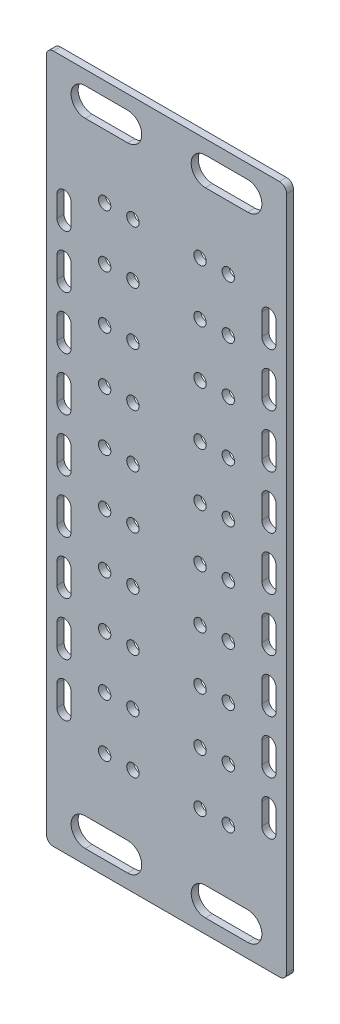
SolidWorks part; units mm, degrees
ref_plane "Plano frontal" through (0, 0, 0) normal (0, 0, 1) x (1, 0, 0)
ref_plane "Plano superior" through (0, 0, 0) normal (0, 1, 0) x (1, 0, 0)
ref_plane "Plano direito" through (0, 0, 0) normal (1, 0, 0) x (0, 0, -1)
sketch "Esboço1" plane through (0, 0, 0) normal (0, 0, 1) x (1, 0, 0)
  line L1 (0, 0) -> (68, 0)
  line L2 (0, 0) -> (0, 195)
  line L3 (0, 195) -> (68, 195)
  line L4 (68, 0) -> (68, 195)
  point P5 (67.3107, 195)
  dimension "D1" = 195
  dimension "D2" = 68
base flange "Flange-base1" sketch "Esboço1" thickness 2 reverse thickness direction no parameters "D1"=0.7366
fillet "Filete1" radius 2 4 edges at (0, 0, -1) (68, 0, -1) (0, 195, -1) (68, 195, -1)
sketch "Esboço2" plane through (0, 0, 0) normal (0, 0, 1) x (1, 0, 0)
  line L0 (11, 187) -> (23, 187) construction
  line L1 (11, 191) -> (23, 191)
  line L2 (11, 183) -> (23, 183)
  line L3 (34, 0) -> (34, 195) construction
  line L4 (2, 0) -> (66, 0) construction
  line L5 (0, 97.5) -> (68, 97.5) construction
  line L6 (0, 193) -> (0, 2) construction
  line L7 (68, 2) -> (68, 193) construction
  line L8 (66, 195) -> (2, 195) construction
  line L9 (5, 160.5) -> (5, 154.5) construction
  line L10 (57, 187) -> (45, 187) construction
  line L11 (57, 191) -> (45, 191)
  line L12 (57, 183) -> (45, 183)
  line L13 (11, 8) -> (23, 8) construction
  line L14 (11, 4) -> (23, 4)
  line L15 (11, 12) -> (23, 12)
  line L16 (57, 8) -> (45, 8) construction
  line L17 (57, 4) -> (45, 4)
  line L18 (57, 12) -> (45, 12)
  line L20 (16.5, 165) -> (24.5, 165) construction
  line L21 (7, 160.5) -> (7, 154.5)
  line L22 (3, 160.5) -> (3, 154.5)
  line L23 (16.5, 165) -> (16.5, 150) construction
  line L24 (63, 160.5) -> (63, 154.5) construction
  line L25 (65, 160.5) -> (65, 154.5)
  line L26 (61, 160.5) -> (61, 154.5)
  line L27 (63, 145.5) -> (63, 139.5) construction
  line L28 (65, 145.5) -> (65, 139.5)
  line L29 (61, 145.5) -> (61, 139.5)
  line L30 (63, 130.5) -> (63, 124.5) construction
  line L31 (65, 130.5) -> (65, 124.5)
  line L32 (61, 130.5) -> (61, 124.5)
  line L33 (63, 115.5) -> (63, 109.5) construction
  line L34 (65, 115.5) -> (65, 109.5)
  line L35 (61, 115.5) -> (61, 109.5)
  line L36 (63, 100.5) -> (63, 94.5) construction
  line L37 (65, 100.5) -> (65, 94.5)
  line L38 (61, 100.5) -> (61, 94.5)
  line L39 (63, 85.5) -> (63, 79.5) construction
  line L40 (65, 85.5) -> (65, 79.5)
  line L41 (61, 85.5) -> (61, 79.5)
  line L42 (63, 70.5) -> (63, 64.5) construction
  line L43 (65, 70.5) -> (65, 64.5)
  line L44 (61, 70.5) -> (61, 64.5)
  line L45 (63, 55.5) -> (63, 49.5) construction
  line L46 (65, 55.5) -> (65, 49.5)
  line L47 (61, 55.5) -> (61, 49.5)
  line L48 (5, 145.5) -> (5, 139.5) construction
  line L49 (7, 145.5) -> (7, 139.5)
  line L50 (3, 145.5) -> (3, 139.5)
  line L51 (5, 130.5) -> (5, 124.5) construction
  line L52 (7, 130.5) -> (7, 124.5)
  line L53 (3, 130.5) -> (3, 124.5)
  line L54 (5, 115.5) -> (5, 109.5) construction
  line L55 (7, 115.5) -> (7, 109.5)
  line L56 (3, 115.5) -> (3, 109.5)
  line L57 (5, 100.5) -> (5, 94.5) construction
  line L58 (7, 100.5) -> (7, 94.5)
  line L59 (3, 100.5) -> (3, 94.5)
  line L60 (5, 85.5) -> (5, 79.5) construction
  line L61 (7, 85.5) -> (7, 79.5)
  line L62 (3, 85.5) -> (3, 79.5)
  line L63 (5, 70.5) -> (5, 64.5) construction
  line L64 (7, 70.5) -> (7, 64.5)
  line L65 (3, 70.5) -> (3, 64.5)
  line L66 (5, 55.5) -> (5, 49.5) construction
  line L67 (7, 55.5) -> (7, 49.5)
  line L68 (3, 55.5) -> (3, 49.5)
  line L69 (5, 40.5) -> (5, 34.5) construction
  line L70 (7, 40.5) -> (7, 34.5)
  line L71 (3, 40.5) -> (3, 34.5)
  line L72 (63, 40.5) -> (63, 34.5) construction
  line L73 (65, 40.5) -> (65, 34.5)
  line L74 (61, 40.5) -> (61, 34.5)
  arc A0 (11, 191) -> (11, 183) centre (11, 187) ccw
  arc A1 (23, 183) -> (23, 191) centre (23, 187) ccw
  arc A2 (57, 191) -> (57, 183) centre (57, 187) cw
  arc A3 (45, 183) -> (45, 191) centre (45, 187) cw
  arc A4 (11, 4) -> (11, 12) centre (11, 8) cw
  arc A5 (23, 12) -> (23, 4) centre (23, 8) cw
  arc A6 (57, 4) -> (57, 12) centre (57, 8) ccw
  arc A7 (45, 12) -> (45, 4) centre (45, 8) ccw
  circle A8 centre (16.5, 165) radius 1.75
  circle A9 centre (24.5, 165) radius 1.75
  circle A10 centre (43.5, 165) radius 1.75
  circle A11 centre (51.5, 165) radius 1.75
  circle A12 centre (43.5, 150) radius 1.75
  circle A13 centre (51.5, 150) radius 1.75
  circle A14 centre (43.5, 135) radius 1.75
  circle A15 centre (51.5, 135) radius 1.75
  circle A16 centre (43.5, 120) radius 1.75
  circle A17 centre (51.5, 120) radius 1.75
  circle A18 centre (43.5, 105) radius 1.75
  circle A19 centre (51.5, 105) radius 1.75
  circle A20 centre (16.5, 150) radius 1.75
  circle A21 centre (24.5, 150) radius 1.75
  circle A22 centre (16.5, 135) radius 1.75
  circle A23 centre (24.5, 135) radius 1.75
  circle A24 centre (16.5, 120) radius 1.75
  circle A25 centre (24.5, 120) radius 1.75
  circle A26 centre (16.5, 105) radius 1.75
  circle A27 centre (24.5, 105) radius 1.75
  circle A28 centre (16.5, 90) radius 1.75
  circle A29 centre (24.5, 90) radius 1.75
  circle A30 centre (43.5, 90) radius 1.75
  circle A31 centre (51.5, 90) radius 1.75
  circle A32 centre (16.5, 75) radius 1.75
  circle A33 centre (24.5, 75) radius 1.75
  circle A34 centre (43.5, 75) radius 1.75
  circle A35 centre (51.5, 75) radius 1.75
  circle A36 centre (16.5, 60) radius 1.75
  circle A37 centre (24.5, 60) radius 1.75
  circle A38 centre (43.5, 60) radius 1.75
  circle A39 centre (51.5, 60) radius 1.75
  circle A40 centre (16.5, 45) radius 1.75
  circle A41 centre (24.5, 45) radius 1.75
  circle A42 centre (43.5, 45) radius 1.75
  circle A43 centre (51.5, 45) radius 1.75
  circle A44 centre (16.5, 30) radius 1.75
  circle A45 centre (24.5, 30) radius 1.75
  circle A46 centre (43.5, 30) radius 1.75
  circle A47 centre (51.5, 30) radius 1.75
  arc A48 (7, 160.5) -> (3, 160.5) centre (5, 160.5) ccw
  arc A49 (3, 154.5) -> (7, 154.5) centre (5, 154.5) ccw
  arc A50 (65, 160.5) -> (61, 160.5) centre (63, 160.5) ccw
  arc A51 (61, 154.5) -> (65, 154.5) centre (63, 154.5) ccw
  arc A52 (65, 145.5) -> (61, 145.5) centre (63, 145.5) ccw
  arc A53 (61, 139.5) -> (65, 139.5) centre (63, 139.5) ccw
  arc A54 (65, 130.5) -> (61, 130.5) centre (63, 130.5) ccw
  arc A55 (61, 124.5) -> (65, 124.5) centre (63, 124.5) ccw
  arc A56 (65, 115.5) -> (61, 115.5) centre (63, 115.5) ccw
  arc A57 (61, 109.5) -> (65, 109.5) centre (63, 109.5) ccw
  arc A58 (65, 100.5) -> (61, 100.5) centre (63, 100.5) ccw
  arc A59 (61, 94.5) -> (65, 94.5) centre (63, 94.5) ccw
  arc A60 (65, 85.5) -> (61, 85.5) centre (63, 85.5) ccw
  arc A61 (61, 79.5) -> (65, 79.5) centre (63, 79.5) ccw
  arc A62 (65, 70.5) -> (61, 70.5) centre (63, 70.5) ccw
  arc A63 (61, 64.5) -> (65, 64.5) centre (63, 64.5) ccw
  arc A64 (65, 55.5) -> (61, 55.5) centre (63, 55.5) ccw
  arc A65 (61, 49.5) -> (65, 49.5) centre (63, 49.5) ccw
  arc A66 (7, 145.5) -> (3, 145.5) centre (5, 145.5) ccw
  arc A67 (3, 139.5) -> (7, 139.5) centre (5, 139.5) ccw
  arc A68 (7, 130.5) -> (3, 130.5) centre (5, 130.5) ccw
  arc A69 (3, 124.5) -> (7, 124.5) centre (5, 124.5) ccw
  arc A70 (7, 115.5) -> (3, 115.5) centre (5, 115.5) ccw
  arc A71 (3, 109.5) -> (7, 109.5) centre (5, 109.5) ccw
  arc A72 (7, 100.5) -> (3, 100.5) centre (5, 100.5) ccw
  arc A73 (3, 94.5) -> (7, 94.5) centre (5, 94.5) ccw
  arc A74 (7, 85.5) -> (3, 85.5) centre (5, 85.5) ccw
  arc A75 (3, 79.5) -> (7, 79.5) centre (5, 79.5) ccw
  arc A76 (7, 70.5) -> (3, 70.5) centre (5, 70.5) ccw
  arc A77 (3, 64.5) -> (7, 64.5) centre (5, 64.5) ccw
  arc A78 (7, 55.5) -> (3, 55.5) centre (5, 55.5) ccw
  arc A79 (3, 49.5) -> (7, 49.5) centre (5, 49.5) ccw
  arc A80 (7, 40.5) -> (3, 40.5) centre (5, 40.5) ccw
  arc A81 (3, 34.5) -> (7, 34.5) centre (5, 34.5) ccw
  arc A82 (65, 40.5) -> (61, 40.5) centre (63, 40.5) ccw
  arc A83 (61, 34.5) -> (65, 34.5) centre (63, 34.5) ccw
  point P2 (17, 187)
  point P21 (51, 187)
  point P28 (17, 8)
  point P35 (51, 8)
  point P46 (20.5, 165)
  point P125 (5, 157.5)
  point P131 (16.5, 157.5)
  point P133 (5, 37.5)
  point P136 (63, 157.5)
  point P143 (63, 142.5)
  point P150 (63, 127.5)
  point P157 (63, 112.5)
  point P164 (63, 97.5)
  point P171 (63, 82.5)
  point P178 (63, 67.5)
  point P185 (63, 52.5)
  point P192 (5, 142.5)
  point P199 (5, 127.5)
  point P206 (5, 112.5)
  point P213 (5, 97.5)
  point P220 (5, 82.5)
  point P227 (5, 67.5)
  point P234 (5, 52.5)
  point P245 (63, 37.5)
  dimension "D1" = 4
  dimension "D2" = 20
  dimension "D5" = 3.5
  dimension "D6" = 3.5
  dimension "D12" = 2
  dimension "D13" = 10
  dimension "D3" = 8
  dimension "D4" = 17
  dimension "D7" = 8
  dimension "D8" = 30
  dimension "D11" = 15
  dimension "D14" = 5
  dimension "D15" = 2
  dimension "D17" = 20.5
  dimension "D18" = 19
  dimension "D9" = 2
  dimension "D10" = 10
  dimension "D16" = 9
extrude "Corte-extrusão1" cut sketch "Esboço2" against normal blind 10 normal cut yes
sketch "Curva-Linhas1" [suppressed] plane through (0, 0, 0) normal (0, 1, 0) x (1, 0, 0)
sketch "Caixa delimitadora1" [suppressed] plane through (0, 0, 0) normal (0, 1, 0) x (1, 0, 0)
sheet metal parameters "Chapa metálica1" thickness 2 parameters "D1"=0.7366
flat pattern "Padrão-Plano1" [suppressed]
sketch "Curva-Linhas2" plane through (0, 0, 0) normal (0, 1, 0) x (1, 0, 0)
sketch3d "Caixa delimitadora2" [suppressed]
  line L0 (67.9999, 0, 0) -> (68, 195, 0) construction
  line L1 (0, 0, 0) -> (0.0001, 195, 0) construction
  line L2 (67.9999, 0, 0) -> (0, 0, 0) construction
  line L3 (68, 195, 0) -> (0.0001, 195, 0) construction
sheet metal parameters "Chapa metálica2" thickness 2 parameters "D1"=0.7366
flat pattern "Padrão-Plano1"
sketch "Curva-Linhas2" plane through (0, 0, 0) normal (0, 1, 0) x (1, 0, 0)
sketch3d "Caixa delimitadora2" [suppressed]
  line L0 (67.9999, 0, 0) -> (68, 195, 0) construction
  line L1 (0, 0, 0) -> (0.0001, 195, 0) construction
  line L2 (67.9999, 0, 0) -> (0, 0, 0) construction
  line L3 (68, 195, 0) -> (0.0001, 195, 0) construction
